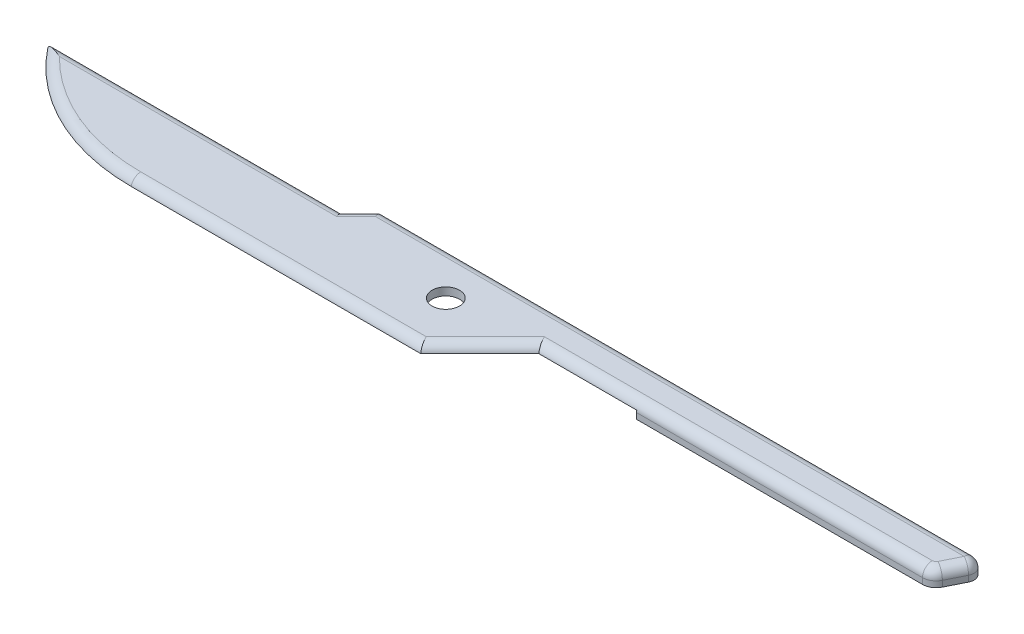
SolidWorks part; units mm, degrees
material "Stainless Steel (ferritic)"
ref_plane "Front Plane" through (0, 0, 0) normal (0, 0, 1) x (1, 0, 0)
ref_plane "Top Plane" through (0, 0, 0) normal (0, 1, 0) x (1, 0, 0)
ref_plane "Right Plane" through (0, 0, 0) normal (1, 0, 0) x (0, 0, -1)
sketch "Sketch1" plane through (0, 0, 0) normal (0, 1, 0) x (1, 0, 0)
  line L0 (0, 0) -> (19.05, 0)
  line L1 (19.05, 0) -> (20.32, 1.27)
  line L2 (20.32, 1.27) -> (59.69, 1.27)
  line L3 (59.69, 1.27) -> (58.42, -1.27)
  line L4 (58.42, -1.27) -> (33.02, -1.27)
  line L5 (33.02, -1.27) -> (29.21, -5.08)
  line L6 (29.21, -5.08) -> (10.4727, -5.08)
  arc A0 (10.4727, -5.08) -> (0, 0) centre (10.4727, 8.255) cw
  dimension "D9" = 13.335
  dimension "D1" = 59.69
  dimension "D2" = 19.05
  dimension "D3" = 39.37
  dimension "D4" = 5.08
  dimension "D5" = 2.54
  dimension "D6" = 25.4
  dimension "D7" = 12.7
  dimension "D8" = 1.27
extrude "Boss-Extrude1" add sketch "Sketch1" along normal blind 1.016
sketch "Sketch2" plane through (0, 0, 0) normal (0, -1, 0) x (1, 0, 0)
  line L1 (39.37, 1.27) -> (39.37, -1.27)
  line L8 (0, 0) -> (19.05, 0)
  line L9 (19.05, 0) -> (20.32, -1.27)
  line L11 (20.32, -1.27) -> (59.69, -1.27)
  line L12 (59.69, -1.27) -> (58.42, 1.27)
  line L13 (58.42, 1.27) -> (33.02, 1.27)
  line L21 (33.02, 1.27) -> (29.21, 5.08)
  line L22 (29.21, 5.08) -> (10.4727, 5.08)
  line L23 (0, 0) -> (19.05, 0)
  line L24 (19.05, 0) -> (20.32, -1.27)
  line L25 (20.32, -1.27) -> (39.37, -1.27)
  line L27 (39.37, 1.27) -> (33.02, 1.27)
  line L28 (33.02, 1.27) -> (29.21, 5.08)
  line L29 (29.21, 5.08) -> (10.4727, 5.08)
  arc A1 (10.4727, 5.08) -> (0, 0) centre (10.4727, -8.255) ccw
  arc A3 (10.4727, 5.08) -> (0, 0) centre (10.4727, -8.255) ccw
  dimension "D2" = 20.32
  dimension "D1" = 0
extrude "Cut-Extrude1" cut sketch "Sketch2" against normal blind 0.508
fillet "Fillet1" radius 0.635 9 edges at (9.525, 1.016, 0) (19.685, 1.016, -0.635) (40.005, 1.016, -1.27) (59.055, 1.016, 0) (45.72, 1.016, 1.27) (31.115, 1.016, 3.175) (19.8413, 1.016, 5.08) (4.6528, 1.016, 3.743) (59.69, 0.508, -1.27)
fillet "Fillet2" radius 0.889 2 edges at (58.3051, 0.83, 1.084) (58.42, 0.1905, 1.27)
sketch "Sketch3" plane through (0, 0.508, 0) normal (0, -1, 0) x (1, 0, 0)
  line L0 (33.02, 1.27) -> (29.21, 5.08) construction
  line L2 (20.3072, -1.2572) -> (39.37, -1.2572) construction
  circle A0 centre (27.4176, 1.6638) radius 0.889
  point P8 (27.4176, 0.7748)
  dimension "D1" = 1.778
  dimension "D2" = 2.794
  dimension "D3" = 2.032
extrude "Cut-Extrude2" cut sketch "Sketch3" against normal through all
